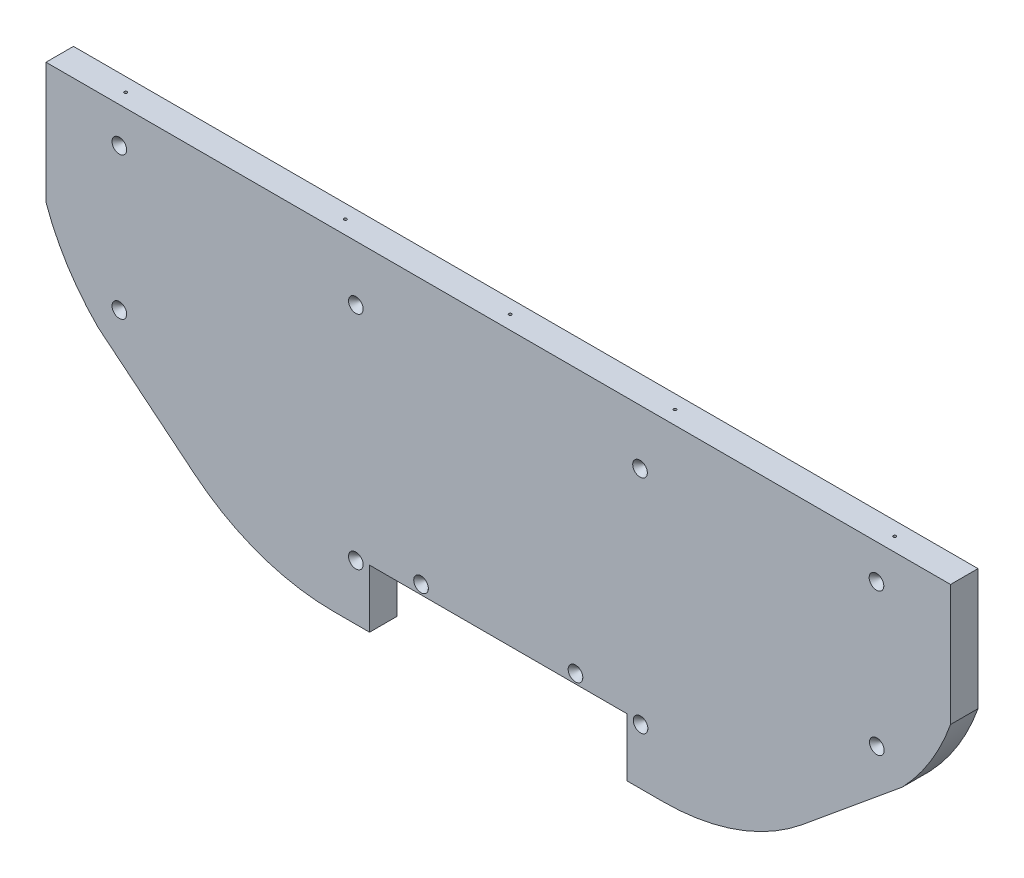
SolidWorks part; units mm, degrees
material "MDF"
ref_plane "Front Plane" through (0, 0, 0) normal (0, 0, 1) x (1, 0, 0)
ref_plane "Top Plane" through (0, 0, 0) normal (0, 1, 0) x (1, 0, 0)
ref_plane "Right Plane" through (0, 0, 0) normal (1, 0, 0) x (0, 0, -1)
sketch "Sketch1" plane through (0, 0, 0) normal (0, 0, 1) x (1, 0, 0)
  line L0 (-394.3667, -87.3125) -> (-394.3667, 23.8125) construction
  line L2 (-618.7885, -233.3625) -> (-593.7568, -233.3625) construction
  line L3 (-394.3667, -87.3125) -> (-394.3667, -3.175)
  line L4 (-497.3744, -199.0142) -> (-427.755, -141.5981)
  line L5 (-709.3267, -233.3625) -> (-593.7568, -233.3625)
  line L6 (-709.3267, -3.175) -> (-709.3267, -233.3625) construction
  line L7 (-1021.7467, -3.175) -> (-396.9067, -3.175) construction
  line L8 (-394.3667, -3.175) -> (-709.3267, -3.175)
  line L9 (-1021.7467, -3.175) -> (-396.9067, -3.175) construction
  line L10 (-976.0267, -152.2395) -> (-918.7391, -199.0142) construction
  line L11 (-1021.7467, -87.3125) -> (-1021.7467, -20.955) construction
  line L12 (-985.5517, -144.4625) -> (-918.7391, -199.0142)
  line L13 (-1021.7467, -87.3125) -> (-1021.7467, -3.175)
  line L14 (-822.3567, -233.3625) -> (-709.3267, -233.3625)
  line L15 (-709.3267, -3.175) -> (-1021.7467, -3.175)
  arc A0 (-427.755, -141.5981) -> (-394.3667, -87.3125) centre (-538.0037, -36.3792) ccw construction
  arc A1 (-593.7568, -233.3625) -> (-497.3744, -199.0142) centre (-593.7568, -80.9625) ccw construction
  arc A2 (-427.755, -141.5981) -> (-394.3667, -87.3125) centre (-538.0037, -36.3792) ccw
  arc A3 (-593.7568, -233.3625) -> (-497.3744, -199.0142) centre (-593.7568, -80.9625) ccw
  arc A4 (-918.7391, -199.0142) -> (-822.3567, -233.3625) centre (-822.3567, -80.9625) ccw construction
  arc A5 (-1021.7467, -87.3125) -> (-985.5517, -144.4625) centre (-878.1098, -36.3792) ccw construction
  arc A6 (-918.7391, -199.0142) -> (-822.3567, -233.3625) centre (-822.3567, -80.9625) ccw
  arc A7 (-1021.7467, -87.3125) -> (-985.5517, -144.4625) centre (-878.1098, -36.3792) ccw
  point P13 (-709.3267, -3.175)
extrude "Boss-Extrude1" add sketch "Sketch1" along normal blind 19.05
hole_wizard "5/64 (0.07813) Diameter Hole1" positions "Sketch2" profile "Sketch3" hole size "5/64" standard "ANSI Inch"
sketch "Sketch2" plane through (-708.0567, 15.875, 6128.5599) normal (0, 1, 0) x (1, 0, 0)
  line L1 (-1.27, 6109.5099) -> (-1.27, 6338.7449) construction
  point P0 (-262.8265, 6157.4524)
  point P6 (-98.7933, 6157.4524)
  point P18 (-262.8265, 6233.6524)
  point P19 (-98.7933, 6233.6524)
  point P22 (-262.8265, 6309.8524)
  point P23 (-98.7933, 6309.8524)
  point P24 (-267.97, 6119.0349)
  point P34 (-115.57, 6119.0349)
  point P37 (-1.27, 6119.0349)
  point P40 (113.03, 6119.0349)
  point P44 (265.43, 6119.0349)
  point P55 (96.2533, 6309.8524)
  point P56 (260.2865, 6309.8524)
  point P59 (96.2533, 6233.6524)
  point P60 (260.2865, 6233.6524)
  point P63 (96.2533, 6157.4524)
  point P64 (260.2865, 6157.4524)
sketch "Sketch3" plane through (-970.8832, 15.875, -28.8925) normal (1, 0, 0) x (0, 0, 1)
  line L0 (0, 0) -> (0, 38.6962)
  line L1 (0, 38.6962) -> (0.9923, 38.1)
  line L2 (0.9923, 38.1) -> (0.9923, 4.7024)
  line L3 (0.9923, 4.7024) -> (5.08, 0)
  line L4 (5.08, 0) -> (0, 0)
  line L5 (-0.9923, 4.7024) -> (-5.08, 0) construction
  line L6 (0, 38.6962) -> (-0.9923, 38.1) construction
  line L7 (0, -6.35) -> (0, 107.95) construction
  dimension "Hole Dia." = 1.9845
  dimension "Hole Depth" = 38.1
  dimension "Near C'Sink Dia." = 10.16
  dimension "Near C'Sink Angle" = 82
  dimension "Drill Angle" = 118
hole_wizard "5/64 (0.07813) Diameter Hole2" positions "Sketch4" profile "Sketch5" hole size "5/64" standard "ANSI Inch"
sketch "Sketch4" plane through (-708.0567, 1936.854, 19.05) normal (0, 0, 1) x (-1, 0, 0)
  line L23 (262.8265, 2088.1084) -> (262.8265, 2038.7486)
  line L24 (262.8265, 2038.7486) -> (262.8265, 1989.3888)
  line L25 (262.8265, 1989.3888) -> (262.8265, 2038.7486)
  line L26 (262.8265, 2038.7486) -> (262.8265, 1989.3888)
  line L27 (262.8265, 1989.3888) -> (262.8265, 1940.029)
  line L33 (98.7933, 2170.2165) -> (98.7933, 2131.8519)
  line L35 (98.7933, 2131.8519) -> (98.7933, 2093.4873)
  line L36 (98.7933, 2093.4873) -> (98.7933, 2055.1227)
  line L37 (98.7933, 2055.1227) -> (98.7933, 2016.7581)
  line L38 (98.7933, 2016.7581) -> (98.7933, 1978.3935)
  line L39 (98.7933, 1978.3935) -> (98.7933, 1940.029)
  line L44 (89.2683, 2123.544) -> (53.561, 2123.544)
  line L46 (53.561, 2123.544) -> (17.8537, 2123.544)
  line L47 (17.8537, 2123.544) -> (-17.8537, 2123.544)
  line L48 (-17.8537, 2123.544) -> (-53.561, 2123.544)
  line L49 (-53.561, 2123.544) -> (-89.2683, 2123.544)
  line L53 (0, 2170.2165) -> (0.2777, 1940.029) construction
  line L55 (-98.3301, 1978.1557) -> (-98.2375, 1939.7912)
  line L56 (-98.4227, 2016.5202) -> (-98.3301, 1978.1557)
  line L57 (-98.5153, 2054.8846) -> (-98.4227, 2016.5202)
  line L58 (-98.6078, 2093.2491) -> (-98.5153, 2054.8846)
  line L59 (-98.7004, 2131.6136) -> (-98.6078, 2093.2491)
  line L60 (-98.793, 2169.978) -> (-98.7004, 2131.6136)
  line L61 (-262.3894, 1988.755) -> (-262.2702, 1939.3954)
  line L62 (-262.5085, 2038.1147) -> (-262.3894, 1988.755)
  line L63 (-262.3894, 1988.755) -> (-262.5085, 2038.1147)
  line L64 (-262.5085, 2038.1147) -> (-262.3894, 1988.755)
  line L65 (-262.6276, 2087.4744) -> (-262.5085, 2038.1147)
  point P71 (262.8265, 1964.7089)
  point P79 (262.8265, 2063.4285)
  point P95 (98.7933, 2131.8519)
  point P103 (98.7933, 1978.3935)
  point P126 (53.561, 2123.544)
  point P134 (-53.561, 2123.544)
  point P162 (-98.3301, 1978.1557)
  point P166 (-98.7004, 2131.6136)
  point P167 (-262.568, 2062.7945)
  point P169 (-262.3298, 1964.0752)
sketch "Sketch5" plane through (-445.727, -27.2212, 19.05) normal (1, 0, 0) x (0, -1, 0)
  line L0 (0, 0) -> (0, 38.6962)
  line L1 (0, 38.6962) -> (0.9923, 38.1)
  line L2 (0.9923, 38.1) -> (0.9923, 4.7024)
  line L3 (0.9923, 4.7024) -> (5.08, 0)
  line L4 (5.08, 0) -> (0, 0)
  line L5 (-0.9923, 4.7024) -> (-5.08, 0) construction
  line L6 (0, 38.6962) -> (-0.9923, 38.1) construction
  line L7 (0, -6.35) -> (0, 107.95) construction
  dimension "Hole Dia." = 1.9845
  dimension "Hole Depth" = 38.1
  dimension "Near C'Sink Dia." = 10.16
  dimension "Near C'Sink Angle" = 82
  dimension "Drill Angle" = 118
sketch "Sketch6" plane through (0, 0, 0) normal (0, 0, -1) x (-1, 0, 0)
  line L1 (797.325, -233.3625) -> (618.7884, -233.3625)
  line L2 (797.325, -233.3625) -> (797.325, -193.04)
  line L3 (797.325, -193.04) -> (618.7884, -193.04)
  line L4 (618.7884, -233.3625) -> (618.7884, -193.04)
extrude "Cut-Extrude1" cut sketch "Sketch6" against normal up to next
